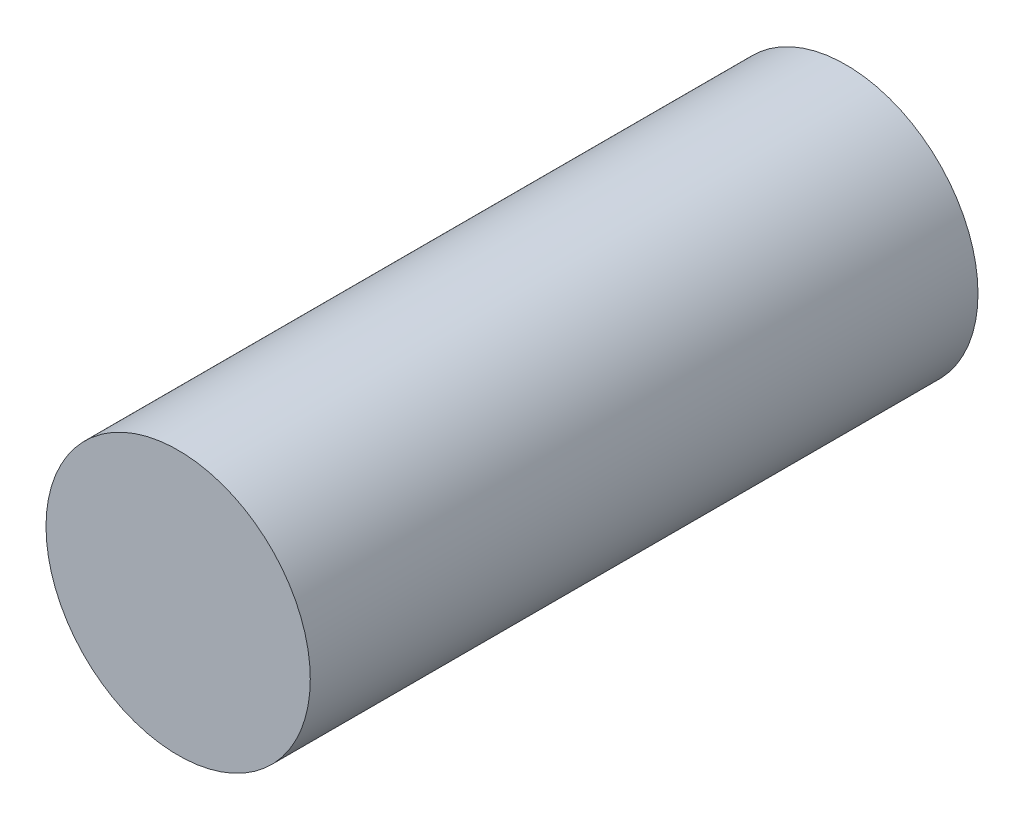
SolidWorks part; units mm, degrees
ref_plane "Front Plane" through (0, 0, 0) normal (0, 0, 1) x (1, 0, 0)
ref_plane "Top Plane" through (0, 0, 0) normal (0, 1, 0) x (1, 0, 0)
ref_plane "Right Plane" through (0, 0, 0) normal (1, 0, 0) x (0, 0, -1)
sketch "Sketch1" plane through (0, 0, 0) normal (0, 0, 1) x (1, 0, 0)
  circle A0 centre (0, 0) radius 30.1625
  dimension "D1" = 60.325
extrude "Boss-Extrude1" add sketch "Sketch1" along normal blind 152.4
